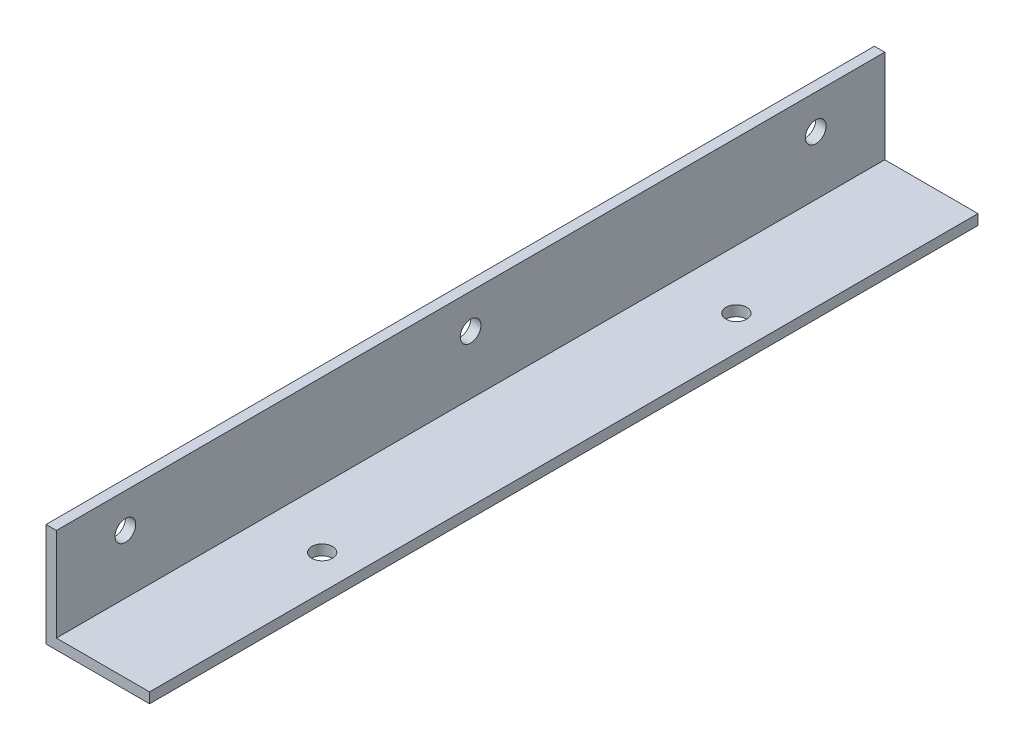
SolidWorks part; units mm, degrees
ref_plane "Plan de face" through (0, 0, 0) normal (0, 0, 1) x (1, 0, 0)
ref_plane "Plan de dessus" through (0, 0, 0) normal (0, 1, 0) x (1, 0, 0)
ref_plane "Plan de droite" through (0, 0, 0) normal (1, 0, 0) x (0, 0, -1)
sketch "Esquisse1" plane through (0, 0, 0) normal (0, 0, 1) x (1, 0, 0)
  line L1 (0, 0) -> (1.5, 0)
  line L2 (0, 0) -> (0, 15)
  line L3 (0, 15) -> (1.5, 15)
  line L4 (1.5, 1.5) -> (1.5, 15)
  line L5 (1.5, 0) -> (15, 0)
  line L7 (1.5, 1.5) -> (15, 1.5)
  line L8 (15, 0) -> (15, 1.5)
  dimension "D1" = 1.5
  dimension "D2" = 1.5
  dimension "D3" = 15
  dimension "D4" = 13.5
  dimension "D5" = 13.5
extrude "Extrusion1" add sketch "Esquisse1" along normal blind 120
sketch "Esquisse2" plane through (0, 0, 0) normal (-1, 0, 0) x (0, 0, 1)
  line L0 (120, 15) -> (0, 15) construction
  line L1 (0, 15) -> (0, 0) construction
  circle A0 centre (60, 10) radius 1.5
  circle A6 centre (59.9101, 7) radius 1.5
  circle A7 centre (9.9101, 10) radius 1.5 [skipped]
  circle A8 centre (110, 7) radius 1.5 [skipped]
  dimension "D1" = 3
  dimension "D2" = 5
  dimension "D3" = 60
extrude "Extrusion2" cut sketch "Esquisse2" against normal through all contours A0 region at (0, 10, 60)
sketch "Esquisse3" plane through (0, 0, 0) normal (0, -1, 0) x (1, 0, 0)
  line L0 (15, 120) -> (15, 0) construction
  line L1 (0, 120) -> (15, 120) construction
  circle A0 centre (10, 90) radius 1.5
  dimension "D1" = 3
  dimension "D2" = 5
  dimension "D3" = 30
extrude "Extrusion3" cut sketch "Esquisse3" against normal blind 120
pattern_linear "Répétition linéaire1" count 2 spacing 60 along (0, 0, -1) of "Extrusion3"
pattern_linear "Répétition linéaire2" count 2 spacing 50 along (0, 0, 1) count 2 spacing 50 along (0, 0, -1) of "Extrusion2"
